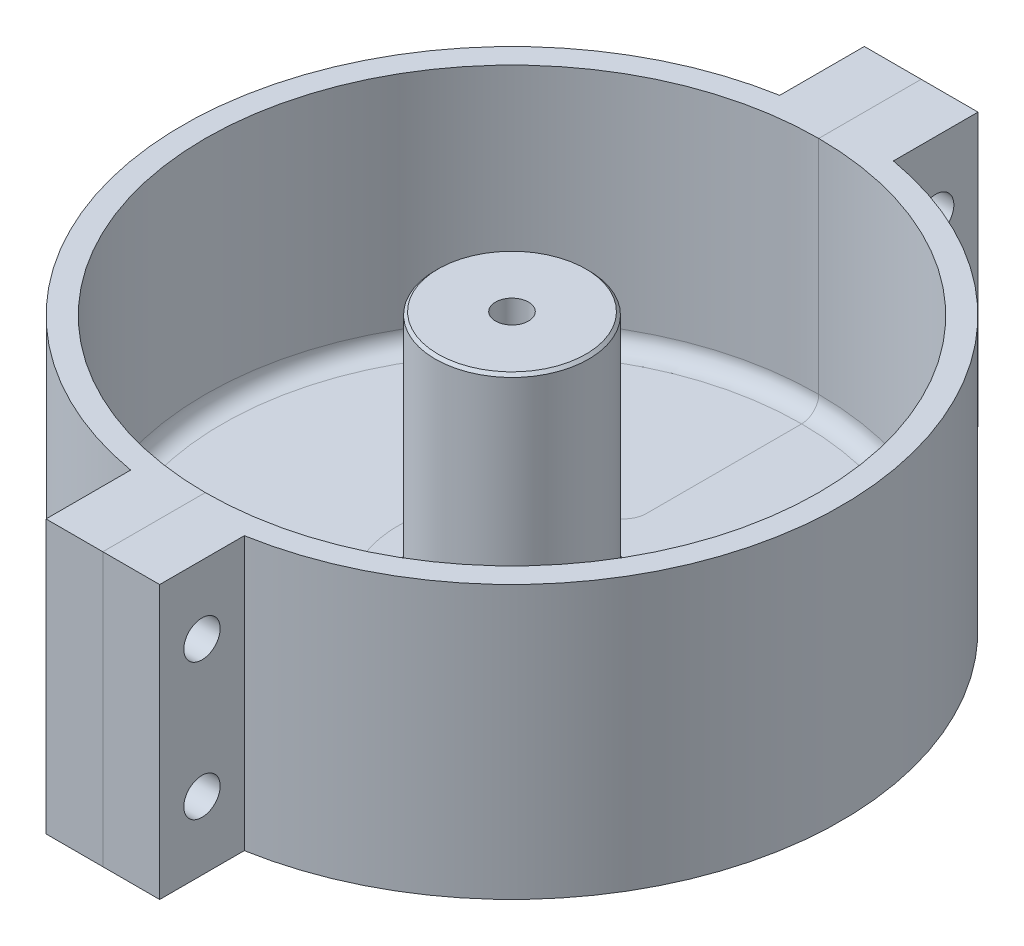
SolidWorks part; units mm, degrees
ref_plane "Front Plane" through (0, 0, 0) normal (0, 0, 1) x (1, 0, 0)
ref_plane "Top Plane" through (0, 0, 0) normal (0, 1, 0) x (1, 0, 0)
ref_plane "Right Plane" through (0, 0, 0) normal (1, 0, 0) x (0, 0, -1)
sketch "Sketch1" plane through (0, 0, 0) normal (0, 1, 0) x (1, 0, 0)
  circle A0 centre (0, 0) radius 26.9875
  circle A1 centre (0, 0) radius 28.9875
  dimension "D1" = 53.975
  dimension "D2" = 2
extrude "Boss-Extrude1" add sketch "Sketch1" along normal blind 24
extrude "Boss-Extrude2" add sketch "Sketch1<2>" along normal blind 3 contours A0 region at (0, 0, 0)
sketch "Sketch1<2>" plane through (0, 0, 0) normal (0, 1, 0) x (1, 0, 0) same geometry as "Sketch1"
fillet "Fillet1" radius 1.5 1 edges at (0, 3, 26.9875)
sketch "Sketch2" plane through (0, 3, 0) normal (0, 1, 0) x (1, 0, 0)
  circle A0 centre (0, 0) radius 6.75
  dimension "D1" = 13.5
extrude "Boss-Extrude3" add sketch "Sketch2" along normal blind 21.3
sketch "Sketch3" plane through (0, 24, 0) normal (0, 1, 0) x (1, 0, 0)
  line L0 (0, 0) -> (0, 45.2463) construction
  line L1 (5, 36) -> (-5, 36)
  line L2 (5, 36) -> (5, 26)
  line L3 (5, 26) -> (-5, 26)
  line L4 (-5, 36) -> (-5, 26)
  circle A0 centre (0, 0) radius 28.9875 construction
  arc A1 (5, 28.553) -> (-5, 28.553) centre (0, 0) ccw
  circle M2 centre (0, 0) radius 28.9875
  dimension "D1" = 10
  dimension "D2" = 26
  dimension "D3" = 10
extrude "Boss-Extrude4" add sketch "Sketch3" against normal up to surface (24 mm away) contours A1 L0 L1 L4 | L0 L2 L1 M2 region at (-2.5253, 24, -32.4204) region at (2.5253, 24, -32.4204) up to face at (0, 0, 28.9875)
hole_wizard "M3 Clearance Hole1" positions "Sketch5" profile "Sketch7" hole size "M3" standard "ANSI Metric" end condition through all
sketch "Sketch5" plane through (-5, 0, 0) normal (-1, 0, 0) x (0, 0, 1)
  line L0 (-36, 24) -> (-28.553, 24) construction
  line L1 (-36, 24) -> (-28.553, 24)
  line L2 (-28.553, 0) -> (-36, 0) construction
  point P0 (-32.2765, 18)
  point P2 (-32.2765, 6)
  point P7 (-32.2765, 24)
  dimension "D1" = 6
  dimension "D2" = 6
sketch "Sketch7" plane through (-5, 18, -32.2765) normal (0, 1, 0) x (0, 0, 1)
  line L0 (0, 0) -> (0, 33.9875)
  line L1 (0, 33.9875) -> (1.6, 33.9875)
  line L2 (1.6, 33.9875) -> (1.6, 0)
  line L5 (1.6, 0) -> (0, 0)
  line L11 (0, -6.35) -> (0, 107.95) construction
  dimension "Thru Hole Dia." = 3.2
  dimension "Thru Hole Depth" = 33.9875
chamfer "Chamfer1" distance 1 angle 45 1 edges at (0, 3, 6.75)
mirror "Mirror1" about plane through (0, 0, 0) normal (0, 0, 1) of "Boss-Extrude4", "M3 Clearance Hole1"
sketch "Sketch8" plane through (0, 24, 0) normal (0, 1, 0) x (1, 0, 0)
  line L0 (0, 36) -> (0, 11.8322)
  line L1 (5, 36) -> (-5, 36) construction
  line L2 (0, -36) -> (0, -11.8322)
  line L3 (5, -36) -> (-5, -36) construction
  arc A0 (-1.6667, 9.8601) -> (-1.6667, -9.8601) centre (0, 0) ccw
  arc A1 (0, -11.8322) -> (-1.6667, -9.8601) centre (-2, -11.8322) ccw
  arc A2 (0, 11.8322) -> (-1.6667, 9.8601) centre (-2, 11.8322) cw
  point P15 (0, 10)
  dimension "D1" = 20
  dimension "D2" = 2
sketch "Sketch9" plane through (0, 24, 0) normal (0, 1, 0) x (1, 0, 0)
  line L0 (26.9735, 0.8701) -> (25.7375, 1)
  line L1 (25.7375, 1) -> (25.7375, -1)
  line L2 (25.7375, -1) -> (26.9735, -0.8701)
  line L3 (0, 0) -> (33.465, 0) construction
  circle A1 centre (0, 0) radius 26.9875 construction
  circle A2 centre (0, 0) radius 26.9875
  circle A3 centre (0, 0) radius 26.9875 construction
  point P6 (26.9875, 0)
  circle M9 centre (0, 0) radius 26.9875
  dimension "D1" = 1.25
  dimension "D2" = 2
  dimension "D3" = 84
extrude "Boss-Extrude5" [suppressed] add sketch "Sketch9" against normal up to surface (21 mm away) contours L3 L1 L2 A2 | L1 L3 L0 M9
fillet "Fillet2" [suppressed] radius 0.5
pattern_circular "CirPattern1" [suppressed] count 28 over 360 of bodies 109
split "Split1" trim tools "Sketch8" bodies to split 106 resulting bodies 107 108
chamfer "Chamfer3" distance 0.25 angle 45 1 edges at (0, 24.3, 6.75)
hole_wizard "M3x0.5 Tapped Hole1" positions "Sketch10" profile "Sketch12" tap size "M3x0.5" standard "ANSI Metric" end condition through all
sketch "Sketch10" plane through (0, 24.3, 0) normal (0, 1, 0) x (1, 0, 0)
  point P0 (0, 0)
sketch "Sketch12" plane through (0, 24.3, 0) normal (1, 0, 0) x (0, 0, 1)
  line L0 (0, 0) -> (0, 24.3)
  line L1 (0, 24.3) -> (1.45, 24.3)
  line L2 (1.45, 24.3) -> (1.45, 0)
  line L5 (1.45, 0) -> (0, 0)
  line L11 (0, -6.35) -> (0, 107.95) construction
  dimension "Thru Tap Drill Dia." = 2.9
  dimension "Thru Tap Drill Depth" = 24.3
cosmetic thread "Hole Thread1" parameters "D2"=3
